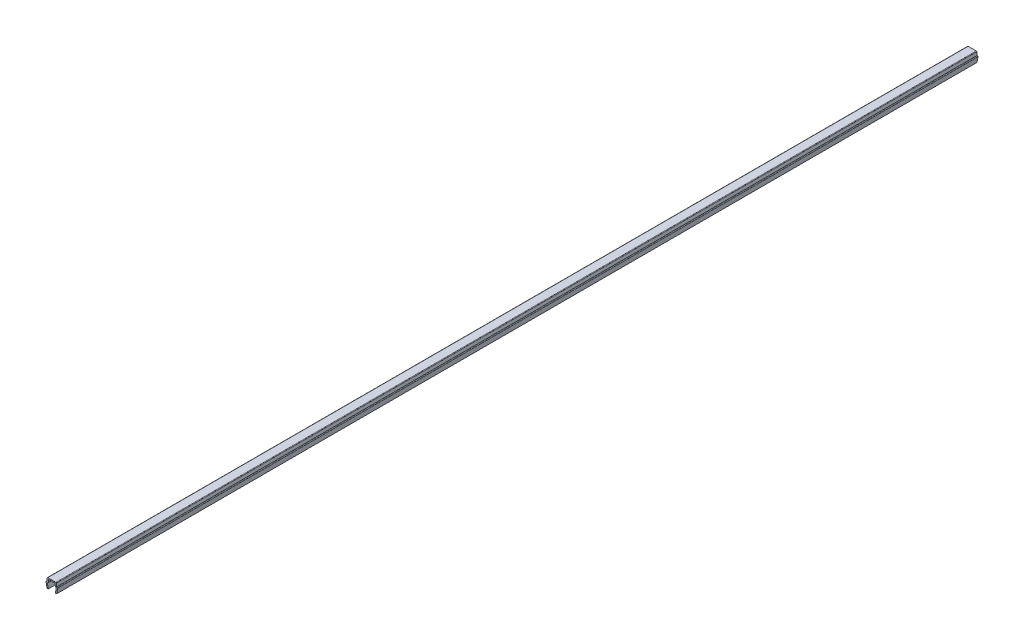
SolidWorks part; units mm, degrees
ref_plane "Front Plane" through (0, 0, 0) normal (0, 0, 1) x (1, 0, 0)
ref_plane "Top Plane" through (0, 0, 0) normal (0, 1, 0) x (1, 0, 0)
ref_plane "Right Plane" through (0, 0, 0) normal (1, 0, 0) x (0, 0, -1)
ref_plane "Plane1" through (0, 0, 0) normal (0, 0, 1) x (1, 0, 0)
sketch "Sketch1" plane through (0, 0, 0) normal (0, 0, 1) x (1, 0, 0)
  line L0 (-3.6, 3.35) -> (-3, 0)
  line L1 (-3, 0) -> (-2.2, 0)
  line L2 (-2.2, 0) -> (-2.7352, 2.9883)
  line L3 (-2.3907, 3.4) -> (-2.2, 3.4)
  line L4 (-2.2, 3.4) -> (-2.0705, 4.8805)
  line L5 (-1.7218, 5.2) -> (1.7218, 5.2)
  line L6 (2.0705, 4.8805) -> (2.2, 3.4)
  line L7 (2.2, 3.4) -> (2.3907, 3.4)
  line L8 (2.7352, 2.9883) -> (2.2, 0)
  line L9 (2.2, 0) -> (3, 0)
  line L10 (3, 0) -> (3.6, 3.35)
  line L11 (3.25, 3.7) -> (3, 3.7)
  line L12 (3, 3.7) -> (2.8355, 5.5805)
  line L13 (2.4868, 5.9) -> (-2.4868, 5.9)
  line L14 (-2.8355, 5.5805) -> (-3, 3.7)
  line L15 (-3, 3.7) -> (-3.25, 3.7)
  arc A0 (-2.7352, 2.9883) -> (-2.3907, 3.4) centre (-2.3907, 3.05) cw
  arc A1 (-2.0705, 4.8805) -> (-1.7218, 5.2) centre (-1.7218, 4.85) cw
  arc A2 (1.7218, 5.2) -> (2.0705, 4.8805) centre (1.7218, 4.85) cw
  arc A3 (2.3907, 3.4) -> (2.7352, 2.9883) centre (2.3907, 3.05) cw
  arc A4 (3.6, 3.35) -> (3.25, 3.7) centre (3.25, 3.35) ccw
  arc A5 (2.8355, 5.5805) -> (2.4868, 5.9) centre (2.4868, 5.55) ccw
  arc A6 (-2.4868, 5.9) -> (-2.8355, 5.5805) centre (-2.4868, 5.55) ccw
  arc A7 (-3.25, 3.7) -> (-3.6, 3.35) centre (-3.25, 3.35) ccw
extrude "Boss-Extrude1" add sketch "Sketch1" against normal mid plane 569.5
